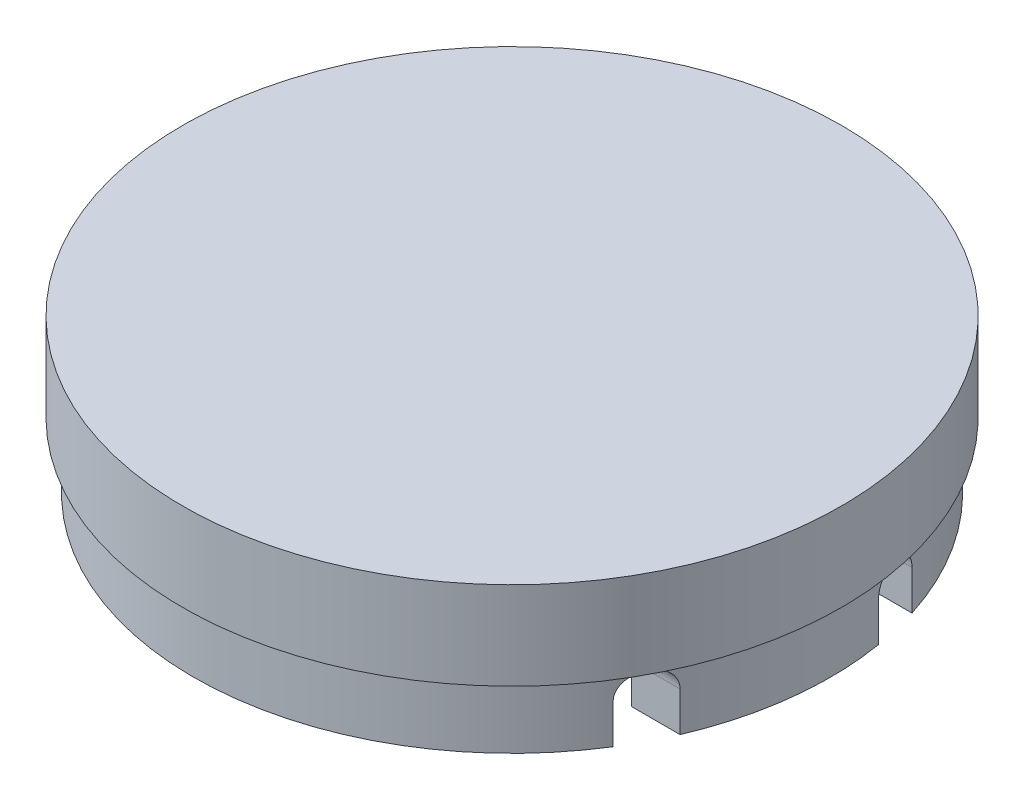
SolidWorks part; units mm, degrees
ref_plane "Front Plane" through (0, 0, 0) normal (0, 0, 1) x (1, 0, 0)
ref_plane "Top Plane" through (0, 0, 0) normal (0, 1, 0) x (1, 0, 0)
ref_plane "Right Plane" through (0, 0, 0) normal (1, 0, 0) x (0, 0, -1)
sketch "Sketch1" plane through (0, 0, 0) normal (0, 0, 1) x (1, 0, 0)
  line L0 (0, 0) -> (0, 92.3285) construction
  line L1 (0, 0) -> (92.075, 0)
  line L2 (92.075, 0) -> (92.075, 19.05)
  line L3 (92.075, 19.05) -> (95.25, 19.05)
  line L4 (95.25, 19.05) -> (95.25, 44.45)
  line L5 (95.25, 44.45) -> (0, 44.45)
  line L6 (0, 44.45) -> (0, 0)
  dimension "D1" = 95.25
  dimension "D2" = 3.175
  dimension "D3" = 19.05
  dimension "D4" = 25.4
revolve "Revolve1" add sketch "Sketch1" angle 360 about L0
ref_plane "Plane1" through (0, 0, 101) normal (0, 0, 1) x (1, 0, 0)
ref_plane "Plane2" through (92.075, 0, 0) normal (1, 0, 0) x (0, 0, -1)
shell "Shell1" thickness 12.7 removed face at (0, 0, -92.075)
sketch "Sketch2" plane through (0, 0, 0) normal (1, 0, 0) x (0, 0, -1)
  line L0 (-42.4802, -11.43) -> (-42.4802, 11.43) construction
  line L1 (-92.075, 0) -> (92.075, 0) construction
  line L2 (-48.8302, -11.43) -> (-48.8302, 11.43)
  line L3 (-36.1302, -11.43) -> (-36.1302, 11.43)
  line L5 (21.4516, -11.43) -> (21.4516, 11.43) construction
  line L6 (15.1016, -11.43) -> (15.1016, 11.43)
  line L7 (27.8016, -11.43) -> (27.8016, 11.43)
  line L8 (-42.4802, -5.7006) -> (-42.4802, 27.8494) construction
  line L11 (21.4516, -4.583) -> (21.4516, 28.967) construction
  line L12 (-92.075, 19.05) -> (92.075, 19.05) construction
  arc A0 (-48.8302, -11.43) -> (-36.1302, -11.43) centre (-42.4802, -11.43) ccw
  arc A1 (-36.1302, 11.43) -> (-48.8302, 11.43) centre (-42.4802, 11.43) ccw
  arc A2 (15.1016, -11.43) -> (27.8016, -11.43) centre (21.4516, -11.43) ccw
  arc A3 (27.8016, 11.43) -> (15.1016, 11.43) centre (21.4516, 11.43) ccw
  point P4 (-42.4802, 0)
  point P10 (21.4516, 0)
  point P34 (-42.4802, 17.78)
  dimension "D2" = 1.27
  dimension "D1" = 12.7
  dimension "D3" = 12.7
extrude "Cut-Extrude2" cut sketch "Sketch2" along normal up to next
ref_plane "Plane3" through (0, 22.225, 0) normal (0, -1, 0) x (-1, 0, 0)
